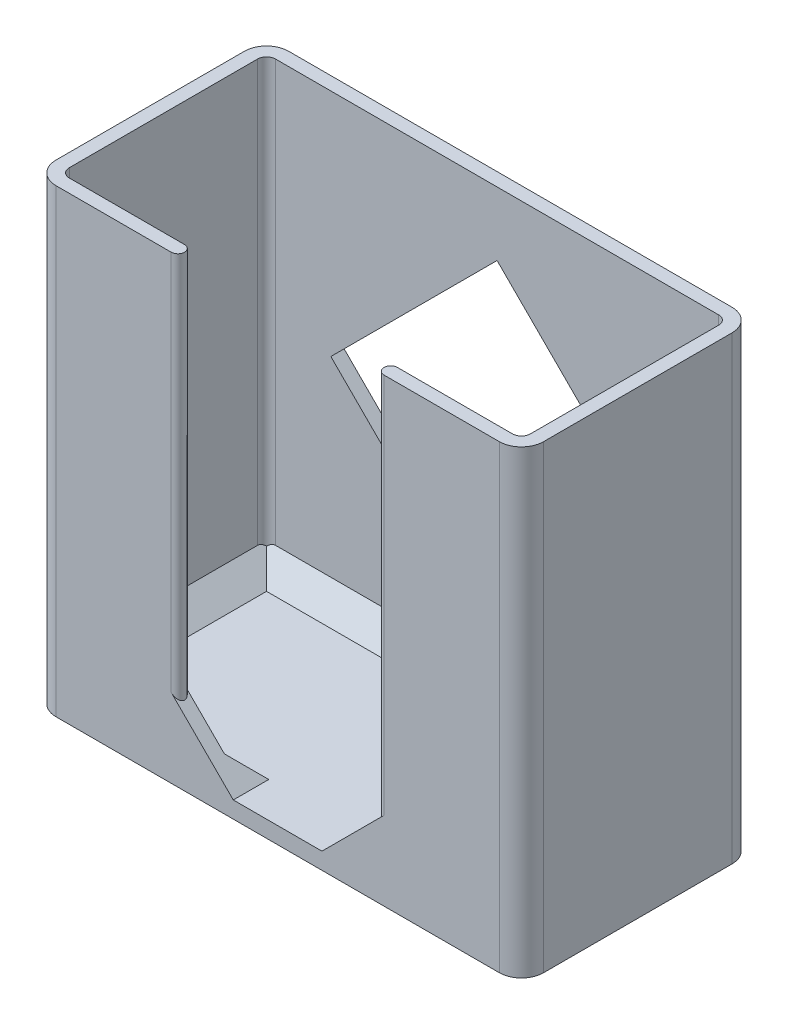
SolidWorks part; units mm, degrees
ref_plane "Plano frontal" through (0, 0, 0) normal (0, 0, 1) x (1, 0, 0)
ref_plane "Plano superior" through (0, 0, 0) normal (0, 1, 0) x (1, 0, 0)
ref_plane "Plano direito" through (0, 0, 0) normal (1, 0, 0) x (0, 0, -1)
sketch "Esboço1" plane through (0, 0, 0) normal (0, 1, 0) x (1, 0, 0)
  line L1 (-20, -10.5) -> (20, -10.5)
  line L2 (-22, -8.5) -> (-22, 8.5)
  line L3 (-20, 10.5) -> (20, 10.5)
  line L4 (22, -8.5) -> (22, 8.5)
  line L5 (-22, -10.5) -> (22, 10.5) construction
  line L6 (-22, 10.5) -> (22, -10.5) construction
  arc A0 (-22, 8.5) -> (-20, 10.5) centre (-20, 8.5) cw
  arc A1 (-20, -10.5) -> (-22, -8.5) centre (-20, -8.5) cw
  arc A2 (20, -10.5) -> (22, -8.5) centre (20, -8.5) ccw
  arc A3 (22, 8.5) -> (20, 10.5) centre (20, 8.5) ccw
  point P0 (0, 0)
  dimension "D3" = 2
  dimension "D4" = 2
  dimension "D1" = 44
  dimension "D2" = 21
extrude "Ressalto-extrusão1" add sketch "Esboço1" along normal blind 1.5
sketch "Esboço3" plane through (0, 1.5, 0) normal (0, 1, 0) x (1, 0, 0)
  line L0 (-20, 9.3) -> (20, 9.3)
  line L1 (-20, -10.5) -> (20, -10.5)
  line L2 (-22, -8.5) -> (-22, 8.5)
  line L3 (-20, 10.5) -> (20, 10.5)
  line L4 (22, -8.5) -> (22, 8.5)
  line L5 (-22, -10.5) -> (22, 10.5) construction
  line L6 (-22, 10.5) -> (22, -10.5) construction
  line L7 (20.8, -8.5) -> (20.8, 8.5)
  line L8 (-20, -9.3) -> (20, -9.3)
  line L9 (-20.8, -8.5) -> (-20.8, 8.5)
  arc A0 (20, 10.5) -> (22, 8.5) centre (20, 8.5) cw
  arc A1 (22, -8.5) -> (20, -10.5) centre (20, -8.5) cw
  arc A2 (-20, -10.5) -> (-22, -8.5) centre (-20, -8.5) cw
  arc A3 (-22, 8.5) -> (-20, 10.5) centre (-20, 8.5) cw
  arc A4 (20, 9.3) -> (20.8, 8.5) centre (20, 8.5) cw
  arc A5 (20.8, -8.5) -> (20, -9.3) centre (20, -8.5) cw
  arc A6 (-20, -9.3) -> (-20.8, -8.5) centre (-20, -8.5) cw
  arc A7 (-20.8, 8.5) -> (-20, 9.3) centre (-20, 8.5) cw
  point P0 (0, 0)
  dimension "D3" = 2
  dimension "D1" = 44
  dimension "D2" = 21
  dimension "D4" = 1.2
extrude "Ressalto-extrusão2" add sketch "Esboço3" along normal blind 40
sketch "Esboço4" plane through (0, 41.5, 0) normal (0, 1, 0) x (1, 0, 0)
  line L0 (-20, -9.3) -> (20, -9.3) construction
  line L1 (-9, -10.8) -> (9, -10.8)
  line L2 (-9, -10.8) -> (-9, -7.8)
  line L3 (-9, -7.8) -> (9, -7.8)
  line L4 (9, -10.8) -> (9, -7.8)
  line L5 (-9, -10.8) -> (9, -7.8) construction
  line L6 (-9, -7.8) -> (9, -10.8) construction
  point P0 (0, -9.3)
  dimension "D1" = 3
  dimension "D2" = 18
extrude "Corte-extrusão1" cut sketch "Esboço4" against normal blind 40
sketch "Esboço5" plane through (0, 0, -10.5) normal (0, 0, -1) x (-1, 0, 0)
  line L1 (0, 5.75) -> (15, 20.75)
  line L2 (15, 20.75) -> (0, 35.75)
  line L3 (0, 35.75) -> (-15, 20.75)
  line L4 (-15, 20.75) -> (0, 5.75)
  circle A0 centre (0, 20.75) radius 15 construction
extrude "Corte-extrusão2" cut sketch "Esboço5" against normal blind 8
chamfer "Chanfro1" distance 5 angle 45 2 edges at (-9, 1.5, 9.9) (9, 1.5, 9.9)
chamfer "Chanfro2" distance 2 angle 45 5 edges at (12, 1.5, 9.3) (20.8, 1.5, 0) (-12, 1.5, 9.3) (-20.8, 1.5, 0) (0, 1.5, -9.3) tangent propagation no
fillet "Filete2" 2 edges at (-9, 24, 10.5) (-9, 24, 9.3) type full round first side face at (0, 18.2, 10.5) second side face at (-12.8, 19.3, 9.3) middle face at (-9, 24, 9.9)
fillet "Filete3" 2 edges at (9, 24, 9.3) (9, 24, 10.5) type full round first side face at (12.8, 19.3, 9.3) second side face at (-0.12, 18.26, 10.5) middle face at (9, 24, 9.9)
